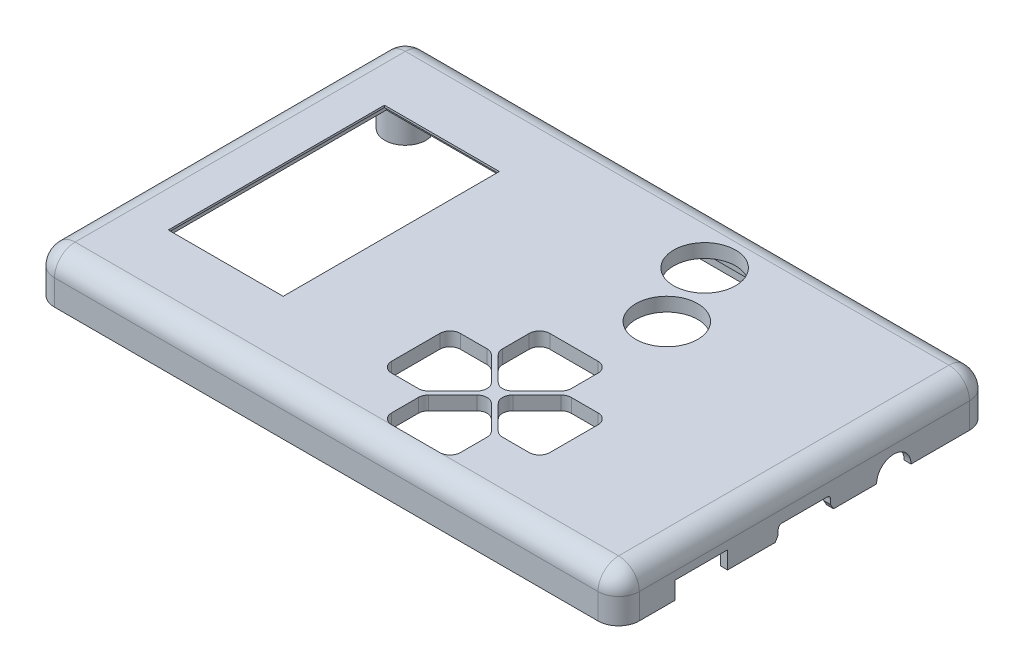
SolidWorks part; units mm, degrees
ref_plane "前视基准面" through (0, 0, 0) normal (0, 0, 1) x (1, 0, 0)
ref_plane "上视基准面" through (0, 0, 0) normal (0, 1, 0) x (1, 0, 0)
ref_plane "右视基准面" through (0, 0, 0) normal (1, 0, 0) x (0, 0, -1)
sketch "草图3" plane through (0, 0, 0) normal (0, 1, 0) x (1, 0, 0)
  line L6 (-42.5, 27) -> (42.5, 27)
  line L7 (-42.5, 27) -> (-42.5, -27)
  line L8 (-42.5, -27) -> (42.5, -27)
  line L9 (42.5, 27) -> (42.5, -27)
  line L10 (-42.5, 27) -> (42.5, -27) construction
  line L11 (-42.5, -27) -> (42.5, 27) construction
  point P0 (0, 0)
  dimension "D1" = 85
  dimension "D2" = 54
extrude "整体外形" add sketch "草图3" along normal blind 6.7
fillet "外形圆角" radius 3 8 edges at (0, 6.7, 27) (-42.5, 6.7, 0) (0, 6.7, -27) (42.5, 6.7, 0) (-42.5, 3.35, -27) (42.5, 3.35, -27) (42.5, 3.35, 27) (-42.5, 3.35, 27)
sketch "草图4" plane through (0, 0, 0) normal (0, -1, 0) x (1, 0, 0)
  line L8 (-40.5, 24) -> (-40.5, -24)
  line L9 (-39.5, -25) -> (39.5, -25)
  line L10 (40.5, -24) -> (40.5, 24)
  line L11 (39.5, 25) -> (-39.5, 25)
  line L12 (-40.5, 24) -> (-40.5, -24)
  line L13 (-39.5, -25) -> (39.5, -25)
  line L14 (40.5, -24) -> (40.5, 24)
  line L15 (39.5, 25) -> (-39.5, 25)
  arc A4 (-40.5, -24) -> (-39.5, -25) centre (-39.5, -24) ccw
  arc A5 (-40.5, -24) -> (-39.5, -25) centre (-39.5, -24) ccw
  arc A6 (39.5, -25) -> (40.5, -24) centre (39.5, -24) ccw
  arc A7 (39.5, -25) -> (40.5, -24) centre (39.5, -24) ccw
  arc A8 (40.5, 24) -> (39.5, 25) centre (39.5, 24) ccw
  arc A9 (40.5, 24) -> (39.5, 25) centre (39.5, 24) ccw
  arc A10 (-39.5, 25) -> (-40.5, 24) centre (-39.5, 24) ccw
  arc A11 (-39.5, 25) -> (-40.5, 24) centre (-39.5, 24) ccw
  dimension "D1" = 2
extrude "内腔" cut sketch "草图4" against normal offset from surface (4.7 mm away) 2 up to face at (0, 6.7, 0)
fillet "内腔圆角" radius 1 8 edges at (-40.5, 4.7, 0) (-40.2071, 4.7, 24.7071) (0, 4.7, 25) (40.2071, 4.7, 24.7071) (40.5, 4.7, 0) (40.2071, 4.7, -24.7071) (0, 4.7, -25) (-40.2071, 4.7, -24.7071)
sketch "草图5" plane through (0, 0, 0) normal (0, -1, 0) x (1, 0, 0)
  line L0 (-41.5, 24) -> (-41.5, -24)
  line L1 (-39.5, -26) -> (39.5, -26)
  line L2 (41.5, -24) -> (41.5, 24)
  line L3 (39.5, 26) -> (-39.5, 26)
  line L20 (-40.5, 24) -> (-40.5, -24)
  line L21 (-39.5, -25) -> (39.5, -25)
  line L22 (40.5, -24) -> (40.5, 24)
  line L23 (39.5, 25) -> (-39.5, 25)
  line L24 (-40.5, 24) -> (-40.5, -24)
  line L25 (-39.5, -25) -> (39.5, -25)
  line L26 (40.5, -24) -> (40.5, 24)
  line L27 (39.5, 25) -> (-39.5, 25)
  arc A0 (-41.5, -24) -> (-39.5, -26) centre (-39.5, -24) ccw
  arc A1 (39.5, -26) -> (41.5, -24) centre (39.5, -24) ccw
  arc A2 (41.5, 24) -> (39.5, 26) centre (39.5, 24) ccw
  arc A3 (-39.5, 26) -> (-41.5, 24) centre (-39.5, 24) ccw
  arc A16 (-40.5, -24) -> (-39.5, -25) centre (-39.5, -24) ccw
  arc A17 (39.5, -25) -> (40.5, -24) centre (39.5, -24) ccw
  arc A18 (40.5, 24) -> (39.5, 25) centre (39.5, 24) ccw
  arc A19 (-39.5, 25) -> (-40.5, 24) centre (-39.5, 24) ccw
  arc A20 (-40.5, -24) -> (-39.5, -25) centre (-39.5, -24) ccw
  arc A21 (39.5, -25) -> (40.5, -24) centre (39.5, -24) ccw
  arc A22 (40.5, 24) -> (39.5, 25) centre (39.5, 24) ccw
  arc A23 (-39.5, 25) -> (-40.5, 24) centre (-39.5, 24) ccw
  dimension "D1" = 1
  dimension "D2" = 2
extrude "咬合（凹）" cut sketch "草图5" against normal blind 2
chamfer "咬合（凹）倒角" distance 1 angle 10 8 edges at (41.5, 2, 0) (40.9142, 2, 25.4142) (40.9142, 2, -25.4142) (0, 2, 26) (0, 2, -26) (-40.9142, 2, 25.4142) (-40.9142, 2, -25.4142) (-41.5, 2, 0) first distance on face at (41.5, 1, 0) first distance on face at (40.7071, 1, 25.2071) first distance on face at (40.7071, 1, -25.2071) first distance on face at (0, 1, 26) first distance on face at (0, 1, -26) first distance on face at (-40.7071, 1, 25.2071) first distance on face at (-40.7071, 1, -25.2071) first distance on face at (-41.5, 1, 0)
extrude "耳机孔" cut sketch "草图6" against normal blind 5
sketch "草图6" plane through (42.5, -7.5, 0) normal (1, 0, 0) x (0, 0, -1)
  circle A0 centre (13, 7.5) radius 2.5
extrude "用户孔" cut sketch "草图19" against normal blind 10
sketch "草图19" plane through (42.5, -7.5, 0) normal (1, 0, 0) x (0, 0, -1)
  line L1 (-18.7884, 10.04) -> (-11.1684, 10.04)
  line L2 (-18.7884, 10.04) -> (-18.7884, 4.96)
  line L3 (-18.7884, 4.96) -> (-11.1684, 4.96)
  line L4 (-11.1684, 10.04) -> (-11.1684, 4.96)
  line L5 (-18.7884, 10.04) -> (-11.1684, 4.96) construction
  line L6 (-18.7884, 4.96) -> (-11.1684, 10.04) construction
  point P0 (-14.9784, 7.5)
sketch "A键" plane through (0, 6.7, 0) normal (0, 1, 0) x (1, 0, 0)
  line L0 (-39.5, 27) -> (39.5, 27) construction
  line L1 (42.5, 24) -> (42.5, -24) construction
  circle A0 centre (13.5, 9) radius 4.5
  dimension "D1" = 9
  dimension "D2" = 18
  dimension "D3" = 29
sketch "B键" plane through (0, 6.7, 0) normal (0, 1, 0) x (1, 0, 0)
  line L0 (-39.5, 27) -> (39.5, 27) construction
  line L1 (42.5, 24) -> (42.5, -24) construction
  circle A0 centre (9.5, 18.5) radius 4.5
  circle A2 centre (13.5, 9) radius 4.5 construction
  dimension "D1" = 8.5
  dimension "D2" = 33
extrude "切除-拉伸8" cut sketch "草图31" against normal blind 10
sketch "草图31" plane through (-42.5, -7.5, 0) normal (-1, 0, 0) x (0, 0, 1)
  line L8 (-24, 7.5) -> (-15.2111, 7.5) construction
  line L25 (16.9, 8.2) -> (14.1, 8.2)
  line L26 (14.1, 8.2) -> (14.1, 7)
  line L27 (14.1, 7) -> (16.9, 7)
  line L28 (16.9, 7) -> (16.9, 8.2)
sketch "草图7" plane through (0, 4.7, 0) normal (0, -1, 0) x (1, 0, 0)
  line L0 (-12.5, 17.25) -> (-12.5, 6.5)
  line L1 (-35.5, 17.25) -> (-12.5, 17.25)
  line L2 (-35.5, 17.25) -> (-35.5, -17.25)
  line L3 (-35.5, -17.25) -> (-12.5, -17.25)
  line L5 (-35.5, 17.25) -> (-12.5, -17.25) construction
  line L6 (-35.5, -17.25) -> (-12.5, 17.25) construction
  line L7 (-9.5, -6.5) -> (-12.5, -6.5)
  line L8 (-9.5, -6.5) -> (-9.5, 6.5)
  line L9 (-9.5, 6.5) -> (-12.5, 6.5)
  line L10 (-12.5, -6.5) -> (-12.5, 6.5) construction
  line L11 (-9.5, -6.5) -> (-12.5, 6.5) construction
  line L12 (-9.5, 6.5) -> (-12.5, -6.5) construction
  line L13 (-12.5, -6.5) -> (-12.5, -17.25)
  line L14 (-42.5, 24) -> (-42.5, -24) construction
  point P0 (-24, 0)
  point P5 (-11, 0)
  dimension "D1" = 23
  dimension "D2" = 34.5
  dimension "D3" = 13
  dimension "D4" = 3
  dimension "D5" = 18.5
extrude "屏幕凹槽" cut sketch "草图7" against normal offset from surface (1.5 mm away) 0.5 up to face at (0, 6.7, 0)
sketch "草图41" plane through (0, 6.2, 0) normal (0, -1, 0) x (1, 0, 0)
  line L0 (-35.5, -17.25) -> (-12.5, -17.25) construction
  line L1 (-35.5, 17.25) -> (-16.3, 17.25)
  line L2 (-35.5, 17.25) -> (-35.5, -17.25)
  line L3 (-35.5, -17.25) -> (-16.3, -17.25)
  line L4 (-16.3, 17.25) -> (-16.3, -17.25)
  line L5 (-35.5, 17.25) -> (-16.3, -17.25) construction
  line L6 (-35.5, -17.25) -> (-16.3, 17.25) construction
  point P4 (-25.9, 0)
  dimension "D1" = 19.2
sketch "草图8" plane through (0, 6.2, 0) normal (0, -1, 0) x (1, 0, 0)
  line L1 (-34.25, 15.71) -> (-17.55, 15.71)
  line L2 (-34.25, 15.71) -> (-34.25, -15.71)
  line L3 (-34.25, -15.71) -> (-17.55, -15.71)
  line L4 (-17.55, 15.71) -> (-17.55, -15.71)
  line L5 (-34.25, 15.71) -> (-17.55, -15.71) construction
  line L6 (-34.25, -15.71) -> (-17.55, 15.71) construction
  point P0 (-25.9, 0)
  dimension "D1" = 31.42
  dimension "D2" = 16.7
extrude "屏幕窗口" cut sketch "草图8" against normal up to next
sketch "草图40" plane through (0, 6.2, 0) normal (0, -1, 0) x (1, 0, 0)
  line L2 (-35, 16.75) -> (-16.8, 16.75)
  line L3 (-35, 16.75) -> (-35, -16.75)
  line L4 (-35, -16.75) -> (-16.8, -16.75)
  line L5 (-16.8, 16.75) -> (-16.8, -16.75)
  line L6 (-35, 16.75) -> (-16.8, -16.75) construction
  line L7 (-35, -16.75) -> (-16.8, 16.75) construction
  point P1 (-25.9, 0)
  dimension "D1" = 18.2
  dimension "D2" = 33.5
extrude "切除-拉伸16" cut sketch "草图40" against normal blind 0.2
sketch "草图42" plane through (0, 6.2, 0) normal (0, -1, 0) x (1, 0, 0)
  line L0 (-16.3, 17.25) -> (-16.3, -17.25) construction
  line L1 (-9.5, -8) -> (-16.3, -8)
  line L2 (-9.5, -8) -> (-9.5, 8)
  line L3 (-9.5, 8) -> (-16.3, 8)
  line L4 (-16.3, -8) -> (-16.3, 8)
  line L5 (-9.5, -8) -> (-16.3, 8) construction
  line L6 (-9.5, 8) -> (-16.3, -8) construction
  line L10 (-9.5, -6.5) -> (-9.5, 6.5) construction
  point P0 (-12.9, 0)
  dimension "D1" = 16
extrude "切除-拉伸17" cut sketch "草图42" against normal blind 0.1
sketch "DPad凹槽轮廓" plane through (0, 6.7, 0) normal (0, 1, 0) x (1, 0, 0)
  line L0 (39.5, -27) -> (-39.5, -27) construction
  line L1 (-42.5, -24) -> (-42.5, 24) construction
  circle A0 centre (10, -12.5) radius 11
  dimension "D1" = 22
  dimension "D2" = 14.5
  dimension "D3" = 52.5
ref_axis "DPad中心轴" through (10, 6.7, 12.5) along (0, 1, 0)
ref_plane "DPad凹槽旋转面" [suppressed] through (0, 0, 12.5) normal (0, 0, 1) x (1, 0, 0)
sketch "草图11" plane through (0, 6.7, 0) normal (0, 1, 0) x (1, 0, 0)
  line L0 (4.5, -12.5) -> (9.5, -12.5) construction
  line L1 (-1.5, -7.5) -> (4.5, -7.5) construction
  line L2 (-1.5, -7.5) -> (-1.5, -17.5) construction
  line L3 (-1.5, -17.5) -> (4.5, -17.5) construction
  line L4 (4.5, -7.5) -> (4.5, -17.5) construction
  line L5 (4.5, -12.5) -> (4.5, -7.5) construction
  line L6 (4.9393, -17.0607) -> (8.4393, -13.5607)
  line L7 (-1.5, -9) -> (-1.5, -16)
  line L8 (0, -17.5) -> (3.8787, -17.5)
  line L9 (8.4393, -11.4393) -> (4.9393, -7.9393)
  line L10 (3.8787, -7.5) -> (0, -7.5)
  line L11 (9.5, -12.5) -> (10, -12.5) construction
  arc A0 (3.8787, -17.5) -> (4.9393, -17.0607) centre (3.8787, -16) ccw
  arc A1 (4.9393, -7.9393) -> (3.8787, -7.5) centre (3.8787, -9) ccw
  arc A2 (-1.5, -16) -> (0, -17.5) centre (0, -16) ccw
  arc A3 (8.4393, -13.5607) -> (8.4393, -11.4393) centre (7.3787, -12.5) ccw
  arc A4 (0, -7.5) -> (-1.5, -9) centre (0, -9) ccw
  dimension "D4" = 1.5
  dimension "D5" = 1.5
  dimension "D6" = 1.5
  dimension "D7" = 1.5
  dimension "D8" = 1.5
  dimension "D1" = 10
  dimension "D2" = 6
  dimension "D3" = 5
  dimension "D9" = 5.5
extrude "DPad按键" cut sketch "草图11" against normal up to next
fillet "圆角4" [suppressed] radius 0.4
sketch "草图17" [suppressed] plane through (0, 0, 12.5) normal (0, 0, 1) x (1, 0, 0)
  line L0 (-1, 7.5) -> (21, 7.5) construction
  line L1 (10, 6) -> (10, 7.5)
  line L2 (10, 7.5) -> (-1, 7.5)
  line L5 (21, 7.5) -> (-1, 7.5) construction
  line L6 (10, 7.5) -> (10, 38.0049) construction
  arc A0 (10, 6) -> (-1, 7.5) centre (10, 47.0833) cw
  point P4 (10, 7.5)
  dimension "D1" = 1.5
revolve "DPad凹槽" [suppressed] cut sketch "草图17" angle 360 about axis through (10, 6.7, 12.5) along (0, 1, 0)
ref_axis "DPad按键定位轴" through (4.5, 9.9725, 12.5) along (0, -1, 0)
pattern_circular "DPad整体" count 4 every 90 about axis through (10, 6.7, 12.5) along (0, 1, 0) of "DPad按键", "圆角4"
extrude "切除-拉伸2" cut sketch "A键" against normal up to surface (2 mm away) up to face at (16.858, 4.7, 12.5)
extrude "切除-拉伸3" cut sketch "B键" against normal up to surface (2 mm away) contours A0 up to face at (13.5, 4.7, -4.5)
sketch "草图22" plane through (0, 6.7, 0) normal (0, 1, 0) x (1, 0, 0)
  line L0 (9.5, 18.5) -> (13.5, 9)
  point P4 (11.5, 13.75)
ref_axis "基准轴1" through (11.5, 6.7, -13.75) along (0, 1, 0)
ref_plane "基准面1" [suppressed] through (13.5, 7.5, -9.3) normal (0.4061, 0, 0.9138) x (0.9138, 0, -0.4061)
sketch "草图24" [suppressed] plane through (13.5, 7.5, -9.3) normal (0.4061, 0, 0.9138) x (0.9138, 0, -0.4061)
  line L1 (4.5, 0) -> (-4.5, 0) construction
  line L2 (-5.5, 0) -> (0, 0)
  line L3 (0, 0) -> (0, -1.5)
  arc A0 (-5.5, 0) -> (0, -1.5) centre (0, 9.3333) ccw
  point P6 (0, 9.3333)
  dimension "D1" = 5.5
  dimension "D2" = 1.5
revolve "切除-旋转1" [suppressed] cut sketch "草图24" angle 180 about L3 reverse direction yes
pattern_circular "阵列(圆周)1" [suppressed] count 2 over 360 about axis through (11.5, 6.7, -13.75) along (0, 1, 0) of bodies 121
sketch "草图27" [suppressed] plane through (-1.2247, 0, -2.7557) normal (0.4061, 0, 0.9138) x (0.9138, 0, -0.4061)
  line L0 (10.6135, 7.5) -> (11.6135, 7.5)
  line L1 (11.6135, 7.5) -> (11.6135, 6.9788)
  arc A0 (10.6135, 7.5) -> (11.6135, 6.9788) centre (16.1135, 16.8333) ccw
  arc A1 (10.6135, 7.5) -> (11.6135, 6.9788) centre (16.1135, 16.8333) ccw construction
extrude "切除-拉伸4" [suppressed] cut sketch "草图27" against normal up to vertex
ref_plane "基准面2" [suppressed] through (14.7247, 0, -6.5443) normal (-0.9138, 0, 0.4061) x (0.4061, 0, 0.9138)
mirror "镜向1" [suppressed] about plane through (14.7247, 0, -6.5443) normal (-0.9138, 0, 0.4061)
sketch "草图28" [suppressed] plane through (0, 7.5, 0) normal (0, 1, 0) x (1, 0, 0)
  line L0 (17.6122, 11.1276) -> (13.6122, 20.1276)
  line L1 (17.6122, 11.1276) -> (9.3878, 7.4724)
  line L2 (13.6122, 20.1276) -> (5.3878, 16.4724)
  line L3 (9.3878, 7.4724) -> (5.3878, 16.4724)
  line L4 (5.3878, 16.4724) -> (9.3878, 7.4724) construction
extrude "切除-拉伸5" [suppressed] cut sketch "草图28" against normal up to vertex
extrude "切除-拉伸10" cut sketch "草图33" against normal blind 10
sketch "草图33" plane through (42.5, -7.5, 0) normal (1, 0, 0) x (0, 0, -1)
  line L16 (3.8, 8.2571) -> (3.8, 8.95)
  line L17 (3.3, 9.45) -> (-3.3, 9.45)
  line L18 (-3.8, 8.95) -> (-3.8, 8.2571)
  line L19 (-3.6536, 7.9036) -> (-2.7464, 6.9964)
  line L20 (-2.3929, 6.85) -> (2.3929, 6.85)
  line L21 (2.7464, 6.9964) -> (3.6536, 7.9036)
  arc A12 (3.6536, 7.9036) -> (3.8, 8.2571) centre (3.3, 8.2571) ccw
  arc A13 (3.8, 8.95) -> (3.3, 9.45) centre (3.3, 8.95) ccw
  arc A14 (-3.3, 9.45) -> (-3.8, 8.95) centre (-3.3, 8.95) ccw
  arc A15 (-3.8, 8.2571) -> (-3.6536, 7.9036) centre (-3.3, 8.2571) ccw
  arc A16 (-2.7464, 6.9964) -> (-2.3929, 6.85) centre (-2.3929, 7.35) ccw
  arc A17 (2.3929, 6.85) -> (2.7464, 6.9964) centre (2.3929, 7.35) ccw
extrude "切除-拉伸11" cut sketch "草图34" against normal blind 10
sketch "草图34" plane through (-42.5, -7.5, 0) normal (-1, 0, 0) x (0, 0, 1)
  line L20 (-5.55, 8.775) -> (-5.55, 7.675)
  line L21 (-5.55, 7.675) -> (5.55, 7.675)
  line L22 (5.55, 7.675) -> (5.55, 8.775)
  line L23 (5.55, 8.775) -> (-5.55, 8.775)
sketch "草图37" plane through (42.5, 0, 0) normal (1, 0, 0) x (0, 0, -1)
  line L5 (-3.8, 0.7571) -> (-4.2371, 0)
  line L6 (-4.2371, 0) -> (-3.25, 0)
  line L7 (3.6536, 0.4036) -> (3.25, 0) construction
  line L8 (3.8, 0.7571) -> (4.2371, 0)
  line L9 (3.25, 0) -> (10.5, 0) construction
  line L10 (4.2371, 0) -> (3.25, 0)
  line L11 (-3.6536, 0.4036) -> (-3.25, 0) construction
  line L12 (3.6536, 0.4036) -> (3.25, 0)
  line L13 (-3.6536, 0.4036) -> (-3.25, 0)
  arc A0 (3.6536, 0.4036) -> (3.8, 0.7571) centre (3.3, 0.7571) ccw construction
  arc A1 (-3.8, 0.7571) -> (-3.6536, 0.4036) centre (-3.3, 0.7571) ccw construction
  arc A2 (3.6536, 0.4036) -> (3.8, 0.7571) centre (3.3, 0.7571) ccw
  arc A3 (-3.8, 0.7571) -> (-3.6536, 0.4036) centre (-3.3, 0.7571) ccw
  dimension "D1" = 60
  dimension "D2" = 60
extrude "切除-拉伸13" cut sketch "草图37" against normal blind 10
sketch "草图38" plane through (-42.5, 0, 0) normal (-1, 0, 0) x (0, 0, 1)
  line L0 (-5.55, 0.175) -> (-5.651, 0)
  line L1 (16.9, 0) -> (24, 0) construction
  line L2 (-5.651, 0) -> (5.651, 0)
  line L3 (5.651, 0) -> (5.55, 0.175)
  line L4 (-5.55, 0.175) -> (5.55, 0.175)
  dimension "D1" = 60
  dimension "D2" = 60
extrude "切除-拉伸14" cut sketch "草图38" against normal up to surface (1 mm away) up to face at (-41.5, 0.4792, 5.1667)
extrude "切除-拉伸15" cut sketch "草图39" against normal blind 10
sketch "草图39" plane through (0, -7.5, -27) normal (0, 0, -1) x (-1, 0, 0)
  line L12 (32.4, 8.2) -> (29.6, 8.2)
  line L13 (29.6, 8.2) -> (29.6, 7)
  line L14 (29.6, 7) -> (32.4, 7)
  line L15 (32.4, 7) -> (32.4, 8.2)
sketch "草图43" plane through (0, 4.7, 0) normal (0, -1, 0) x (1, 0, 0)
  line L0 (-40.5, 24) -> (-40.5, -24) construction
  line L2 (-39.5, 25) -> (39.5, 25) construction
  circle A0 centre (-37, 21.5) radius 1.5
  circle A1 centre (-37, 21.5) radius 3
  dimension "D1" = 3
  dimension "D4" = 6
  dimension "D2" = 3.5
  dimension "D3" = 3.5
extrude "凸台-拉伸1" add sketch "草图43" along normal blind 5.2
pattern_linear "阵列(线性)1" count 2 spacing 74 along (1, 0, 0) count 2 spacing 43 along (0, 0, -1) of "凸台-拉伸1"
